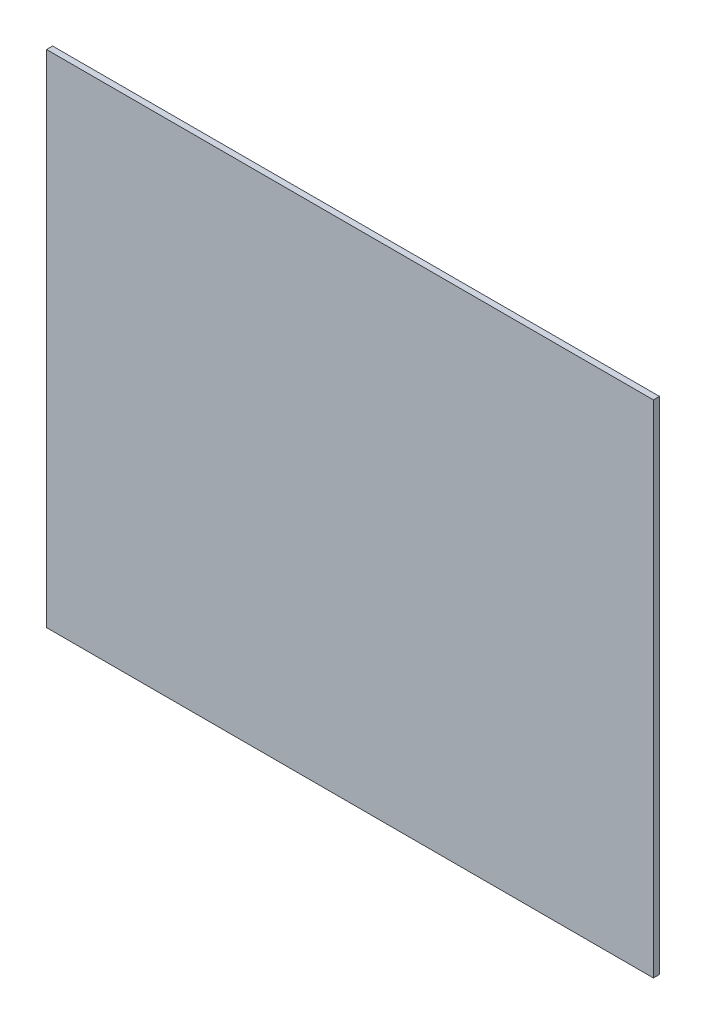
SolidWorks part; units mm, degrees
ref_plane "Alzado" through (0, 0, 0) normal (0, 0, 1) x (1, 0, 0)
ref_plane "Planta" through (0, 0, 0) normal (0, 1, 0) x (1, 0, 0)
ref_plane "Vista lateral" through (0, 0, 0) normal (1, 0, 0) x (0, 0, -1)
sketch "Croquis1" plane through (0, 0, 0) normal (0, 0, 1) x (1, 0, 0)
  line L1 (0, 0) -> (400, 0)
  line L2 (0, 0) -> (0, 330)
  line L3 (0, 330) -> (400, 330)
  line L4 (400, 0) -> (400, 330)
  dimension "D1" = 330
  dimension "D2" = 400
extrude "Saliente-Extruir1" add sketch "Croquis1" along normal blind 4
